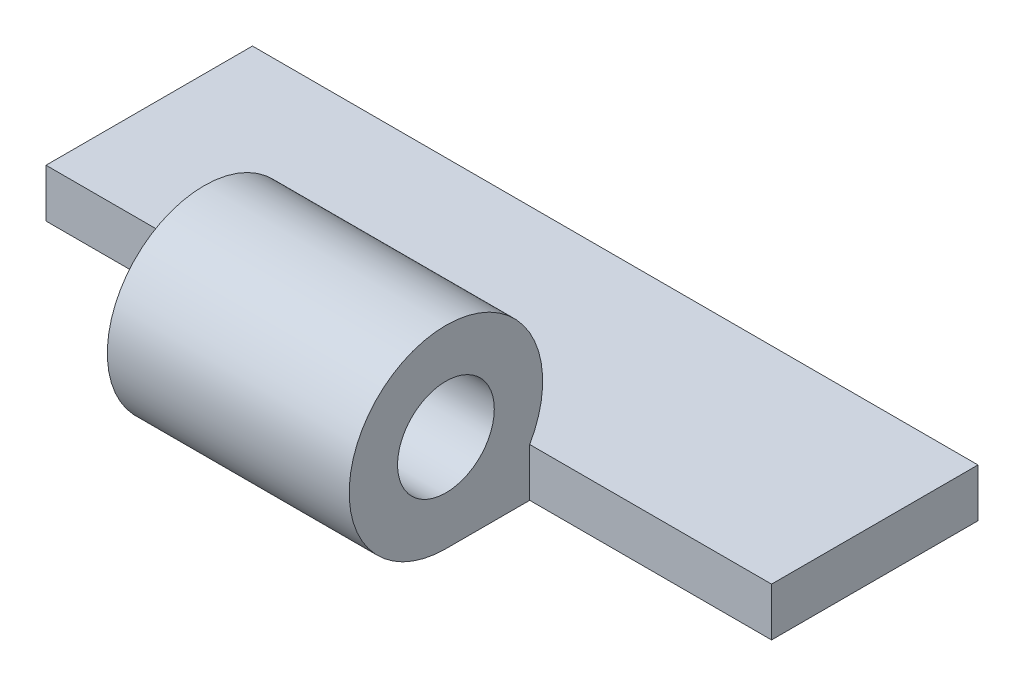
SolidWorks part; units mm, degrees
ref_plane "Ebene vorne" through (0, 0, 0) normal (0, 0, 1) x (1, 0, 0)
ref_plane "Ebene oben" through (0, 0, 0) normal (0, 1, 0) x (1, 0, 0)
ref_plane "Ebene rechts" through (0, 0, 0) normal (1, 0, 0) x (0, 0, -1)
sketch "Skizze1" plane through (0, 0, 0) normal (0, 1, 0) x (1, 0, 0)
  line L1 (0, 0) -> (15, 0)
  line L2 (0, 0) -> (0, 6)
  line L3 (0, 6) -> (15, 6)
  line L4 (15, 0) -> (15, 6)
  dimension "D1" = 15
  dimension "D2" = 6
extrude "Aufsatz-Linear austragen1" add sketch "Skizze1" along normal blind 1
sketch "Skizze2" plane through (15, 0, 0) normal (1, 0, 0) x (0, 0, -1)
  circle A0 centre (0, 2) radius 2
  circle A1 centre (0, 2) radius 1
  dimension "D1" = 2
  dimension "D2" = 1
extrude "Aufsatz-Linear austragen2" add sketch "Skizze2" against normal up to surface (15 mm away) up to face at (0, 0.5, -3)
ref_plane "Tangential Ebene" through (0, 0, -2) normal (0, 0, -1) x (-1, 0, 0)
sketch "Skizze8" plane through (15, 0, 0) normal (1, 0, 0) x (0, 0, -1)
  line L0 (1.7321, 1) -> (1.7321, 0)
  line L1 (1.7321, 0) -> (0, 0)
  line L3 (0, 0) -> (6, 0)
  line L4 (6, 0) -> (6, 1)
  line L5 (6, 1) -> (1.7321, 1)
  line L6 (0, 0) -> (6, 0) construction
  line L7 (6, 0) -> (6, 1) construction
  line L8 (6, 1) -> (1.7321, 1) construction
  arc A1 (1.7321, 1) -> (0, 0) centre (0, 2) ccw
  arc A2 (1.7321, 1) -> (0, 0) centre (0, 2) ccw
  dimension "D1" = 0
extrude "Schnitt-Linear austragen1" cut sketch "Skizze8" against normal blind 5
pattern_linear "Lineares Muster1" count 3 spacing 5 along (-1, 0, 0) skipping (1, 0) of "Schnitt-Linear austragen1"
